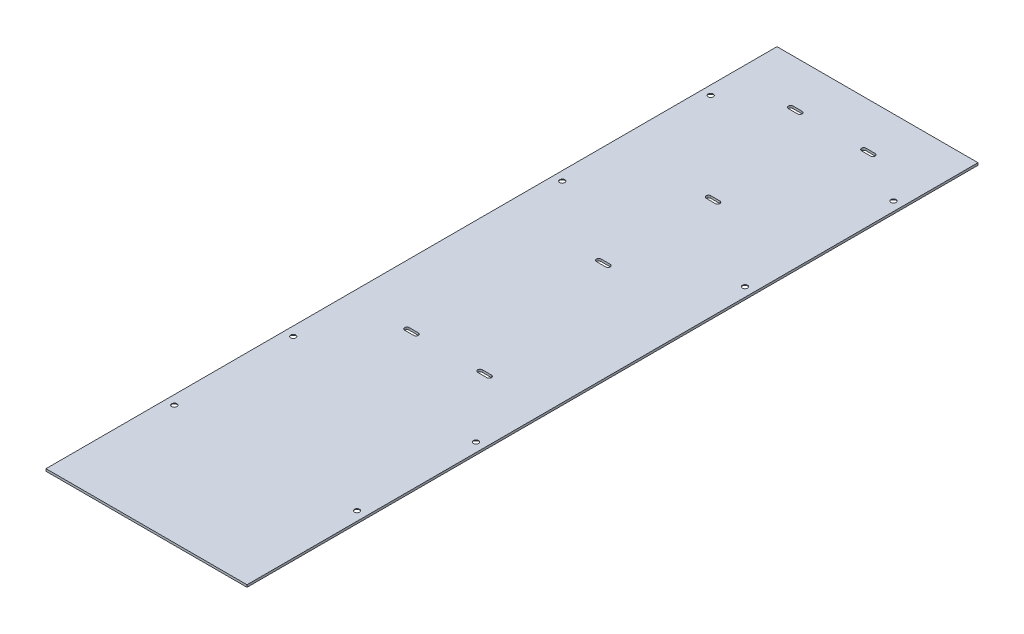
SolidWorks part; units mm, degrees
material "ASTM A36 Steel"
ref_plane "Front Plane" through (0, 0, 0) normal (0, 0, 1) x (1, 0, 0)
ref_plane "Top Plane" through (0, 0, 0) normal (0, 1, 0) x (1, 0, 0)
ref_plane "Right Plane" through (0, 0, 0) normal (1, 0, 0) x (0, 0, -1)
sketch "Sketch1" plane through (0, 0, 0) normal (0, 1, 0) x (1, 0, 0)
  line L0 (0, -508) -> (0, 508) construction
  line L1 (-139.7, -508) -> (139.7, -508)
  line L2 (-139.7, -508) -> (-139.7, 508)
  line L3 (-139.7, 508) -> (139.7, 508)
  line L4 (139.7, -508) -> (139.7, 508)
  line L5 (-139.7, -508) -> (139.7, 508) construction
  line L6 (-139.7, 508) -> (139.7, -508) construction
  line L7 (-139.7, 0) -> (139.7, 0) construction
  line L8 (44.45, -88.9) -> (57.15, -88.9) construction
  line L9 (44.45, -85.725) -> (57.15, -85.725)
  line L10 (44.45, -92.075) -> (57.15, -92.075)
  line L11 (-44.45, -88.9) -> (-57.15, -88.9) construction
  line L12 (-44.45, -85.725) -> (-57.15, -85.725)
  line L13 (-44.45, -92.075) -> (-57.15, -92.075)
  line L14 (57.15, 444.5) -> (44.45, 444.5) construction
  line L15 (57.15, 441.325) -> (44.45, 441.325)
  line L16 (57.15, 447.675) -> (44.45, 447.675)
  line L17 (-57.15, 444.5) -> (-44.45, 444.5) construction
  line L18 (-57.15, 441.325) -> (-44.45, 441.325)
  line L19 (-57.15, 447.675) -> (-44.45, 447.675)
  line L20 (6.35, 279.4) -> (-6.35, 279.4) construction
  line L21 (6.35, 276.225) -> (-6.35, 276.225)
  line L22 (6.35, 282.575) -> (-6.35, 282.575)
  line L23 (-6.35, 127) -> (6.35, 127) construction
  line L24 (-6.35, 130.175) -> (6.35, 130.175)
  line L25 (-6.35, 123.825) -> (6.35, 123.825)
  arc A0 (44.45, -85.725) -> (44.45, -92.075) centre (44.45, -88.9) ccw
  arc A1 (57.15, -92.075) -> (57.15, -85.725) centre (57.15, -88.9) ccw
  arc A2 (-44.45, -85.725) -> (-44.45, -92.075) centre (-44.45, -88.9) cw
  arc A3 (-57.15, -92.075) -> (-57.15, -85.725) centre (-57.15, -88.9) cw
  arc A4 (57.15, 441.325) -> (57.15, 447.675) centre (57.15, 444.5) ccw
  arc A5 (44.45, 447.675) -> (44.45, 441.325) centre (44.45, 444.5) ccw
  arc A6 (-57.15, 441.325) -> (-57.15, 447.675) centre (-57.15, 444.5) cw
  arc A7 (-44.45, 447.675) -> (-44.45, 441.325) centre (-44.45, 444.5) cw
  arc A8 (6.35, 276.225) -> (6.35, 282.575) centre (6.35, 279.4) ccw
  arc A9 (-6.35, 282.575) -> (-6.35, 276.225) centre (-6.35, 279.4) ccw
  arc A10 (-6.35, 130.175) -> (-6.35, 123.825) centre (-6.35, 127) ccw
  arc A11 (6.35, 123.825) -> (6.35, 130.175) centre (6.35, 127) ccw
  point P0 (0, 0)
  point P10 (50.8, -88.9)
  point P18 (-50.8, -88.9)
  point P26 (50.8, 444.5)
  point P34 (-50.8, 444.5)
  point P40 (0, 279.4)
  point P46 (0, 127)
  dimension "D3" = 88.9
  dimension "D4" = 3.175
  dimension "D5" = 12.7
  dimension "D1" = 279.4
  dimension "D2" = 1016
  dimension "D6" = 596.9
  dimension "D7" = 63.5
  dimension "D8" = 228.6
  dimension "D9" = 152.4
extrude "Boss-Extrude1" add sketch "Sketch1" along normal blind 3.175
sketch "Sketch3" plane through (0, 0, 0) normal (0, 1, 0) x (1, 0, 0)
  line L0 (-127, 508) -> (-127, -508) construction
  line L1 (139.7, 508) -> (-139.7, 508) construction
  line L2 (-139.7, -508) -> (139.7, -508) construction
  line L3 (127, 508) -> (127, -508) construction
  line L4 (139.7, -508) -> (139.7, 508) construction
  line L5 (-139.7, 508) -> (-139.7, -508) construction
  point P12 (-127, 403.1742)
  point P13 (127, 403.1742)
  point P14 (-127, 196.85)
  point P15 (127, 196.85)
  point P16 (-127, -177.0126)
  point P17 (127, -177.0126)
  point P18 (-127, -342.4123)
  point P19 (127, -342.4123)
  dimension "D1" = 12.7
  dimension "D2" = 12.7
  dimension "D3" = 104.8258
  dimension "D4" = 311.15
  dimension "D5" = 685.0126
  dimension "D6" = 850.4123
hole_wizard "CSK for 1/4 Flat Head Machine Screw (100)1" positions "Sketch4" profile "Sketch5" countersink size "1/4" standard "ANSI Inch" end condition through all
sketch "Sketch4" plane through (0, 0, 0) normal (0, -1, 0) x (-1, 0, 0)
  point P0 (127, -342.4123)
  point P3 (-127, -342.4123)
  point P6 (-127, -177.0126)
  point P9 (127, -177.0126)
  point P12 (127, 196.85)
  point P15 (-127, 196.85)
  point P18 (-127, 403.1742)
  point P21 (127, 403.1742)
sketch "Sketch5" plane through (-127, 0, 342.4123) normal (1, 0, 0) x (0, 0, -1)
  line L0 (0, 0) -> (0, 3.175)
  line L1 (0, 3.175) -> (3.5712, 3.175)
  line L2 (3.5712, 3.175) -> (3.5712, 2.4063)
  line L3 (3.5712, 2.4063) -> (6.4389, 0)
  line L5 (6.4389, 0) -> (0, 0)
  line L6 (-3.5712, 2.4063) -> (-6.4389, 0) construction
  line L11 (0, -6.35) -> (0, 107.95) construction
  dimension "Thru Hole Dia." = 7.1425
  dimension "Thru Hole Depth" = 3.175
  dimension "Near C'Sink Dia." = 12.8778
  dimension "Near C'Sink Angle" = 100
